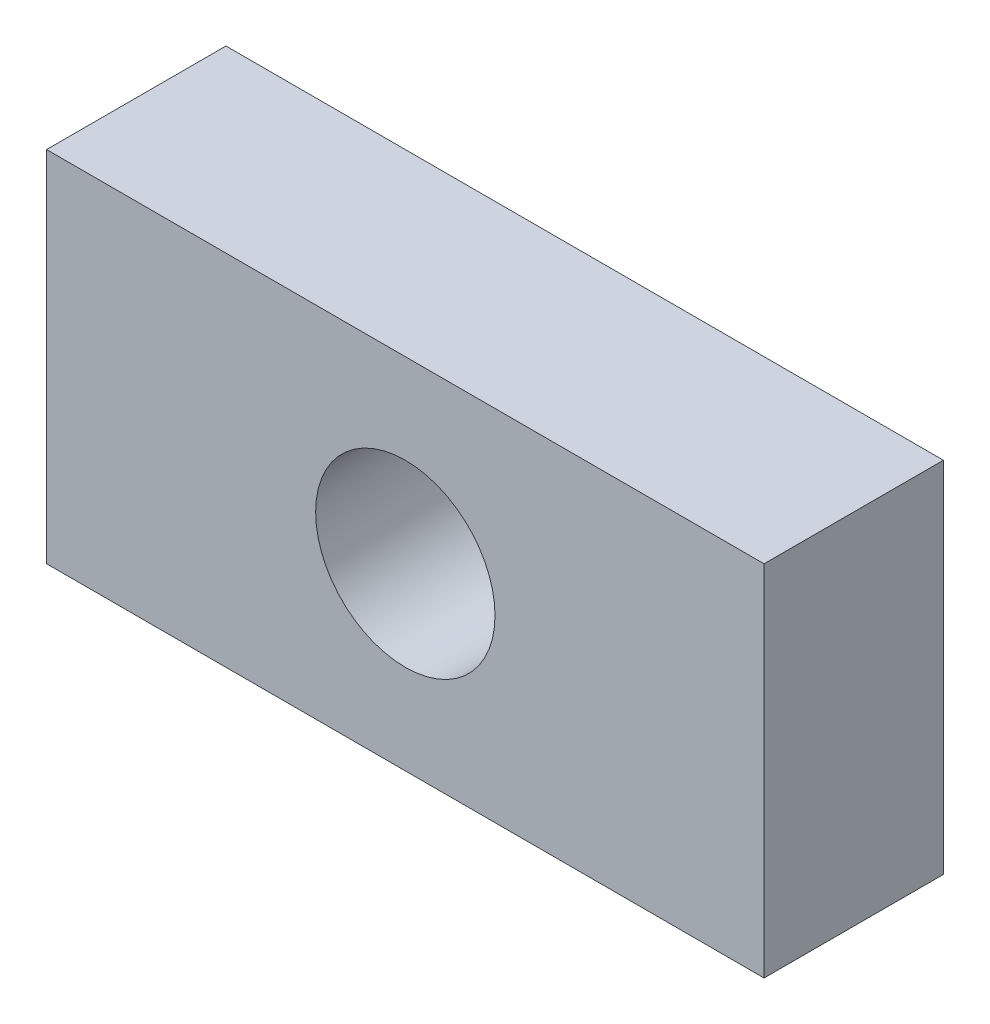
SolidWorks part; units mm, degrees
ref_plane "Front Plane" through (0, 0, 0) normal (0, 0, 1) x (1, 0, 0)
ref_plane "Top Plane" through (0, 0, 0) normal (0, 1, 0) x (1, 0, 0)
ref_plane "Right Plane" through (0, 0, 0) normal (1, 0, 0) x (0, 0, -1)
sketch "Sketch1" plane through (0, 0, 0) normal (0, 0, 1) x (1, 0, 0)
  line L0 (-100, 50) -> (-100, -50)
  line L1 (-100, -50) -> (100, -50)
  line L2 (100, -50) -> (100, 50)
  line L3 (100, 50) -> (-100, 50)
  circle A0 centre (0, 0) radius 25
  dimension "D3" = 50
  dimension "D1" = 200
  dimension "D2" = 100
  dimension "D4" = 100
  dimension "D5" = 50
extrude "Boss-Extrude1" add sketch "Sketch1" along normal blind 50 contours L0 L1 L2 L3
extrude "Cut-Extrude1" cut sketch "Sketch1<3>" along normal through all contours A0
sketch "Sketch1<3>" plane through (0, 0, 0) normal (0, 0, 1) x (1, 0, 0) same geometry as "Sketch1"
